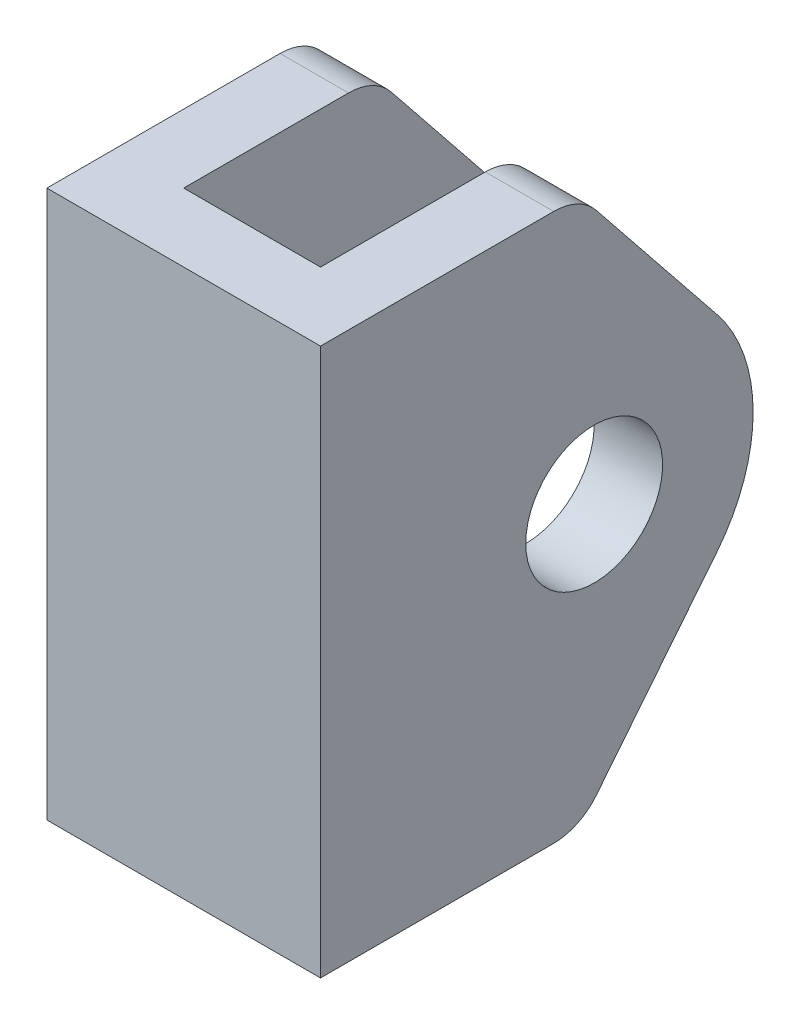
SolidWorks part; units mm, degrees
ref_plane "Front Plane" through (0, 0, 0) normal (0, 0, 1) x (1, 0, 0)
ref_plane "Top Plane" through (0, 0, 0) normal (0, 1, 0) x (1, 0, 0)
ref_plane "Right Plane" through (0, 0, 0) normal (1, 0, 0) x (0, 0, -1)
sketch "Sketch1" plane through (0, 0, 0) normal (0, 1, 0) x (1, 0, 0)
  line L0 (-21.4705, -2.672) -> (-8.7705, -2.672)
  line L1 (-8.7705, -2.672) -> (-8.7705, 19.553)
  line L2 (-8.7705, 19.553) -> (-11.9455, 19.553)
  line L3 (-11.9455, 19.553) -> (-11.9455, 0.503)
  line L4 (-11.9455, 0.503) -> (-18.2955, 0.503)
  line L5 (-18.2955, 0.503) -> (-18.2955, 19.553)
  line L6 (-18.2955, 19.553) -> (-21.4705, 19.553)
  line L7 (-21.4705, 19.553) -> (-21.4705, -2.672)
  dimension "D1" = 3.175
  dimension "D2" = 6.35
  dimension "D3" = 19.05
  dimension "D4" = 3.175
extrude "Boss-Extrude1" add sketch "Sketch1" along normal blind 12.7 and the other way blind 12.7 contours L7 L0 L1 L2 L3 L4 L5 L6
sketch "Sketch3" plane through (-21.4705, 0, 0) normal (-1, 0, 0) x (0, 0, 1)
  line L1 (-10.028, -12.7) -> (-10.028, 0)
  line L2 (-19.553, -12.7) -> (2.672, -12.7) construction
  line L3 (-10.028, 0) -> (-10.028, 12.7)
  line L4 (-19.553, 12.7) -> (2.672, 12.7) construction
  line L6 (-19.553, -12.7) -> (-19.553, 12.7) construction
  circle A0 centre (-10.028, 0) radius 3.175
  dimension "D2" = 6.35
  dimension "D1" = 3.175
extrude "Cut-Extrude1" cut sketch "Sketch3" against normal through all contours L3 A0 L1 | L1 A0 L3 region at (-21.4705, 0, -11.3755) region at (-21.4705, 0, -8.6805)
sketch "Sketch5" plane through (-8.7705, 0, 0) normal (1, 0, 0) x (0, 0, -1)
  line L0 (-2.672, 12.7) -> (19.553, 12.7) construction
  line L1 (-2.672, 12.7) -> (9.3695, 12.7)
  line L2 (9.3695, 12.7) -> (19.553, 0)
  line L3 (19.553, 0) -> (9.3695, -12.7)
  line L5 (9.3695, -12.7) -> (-2.672, -12.7)
  line L6 (-2.672, -12.7) -> (-2.672, 12.7)
  line L7 (19.553, -12.7) -> (19.553, 12.7) construction
  line L8 (9.3695, 12.7) -> (19.0139, 19.0425)
  line L9 (19.0139, 19.0425) -> (26.1277, -0.4938)
  line L10 (26.1277, -0.4938) -> (24.4219, -16.6099)
  line L11 (24.4219, -16.6099) -> (9.7872, -17.8219)
  line L12 (9.7872, -17.8219) -> (9.3695, -12.7)
  line M8 (19.553, -12.7) -> (19.553, 12.7)
  line M9 (19.553, 12.7) -> (-2.672, 12.7)
  line M11 (-2.672, -12.7) -> (19.553, -12.7)
extrude "Cut-Extrude3" cut sketch "Sketch5" against normal blind 17.78 contours L2 M9 M8 | L3 M8 M11 region at (-8.7705, 8.4667, -16.1585) region at (-8.7705, -8.4667, -16.1585)
fillet "Fillet1" radius 7.62 2 edges at (-19.883, 0, -19.553) (-10.358, 0, -19.553)
fillet "Fillet2" radius 2.54 4 edges at (-19.883, -12.7, -9.3695) (-10.358, -12.7, -9.3695) (-10.358, 12.7, -9.3695) (-19.883, 12.7, -9.3695)
sketch "Sketch6" plane through (0, 0, 2.672) normal (0, 0, 1) x (1, 0, 0)
  line L0 (-8.7705, -12.7) -> (-21.4705, 12.7) construction
  circle A0 centre (-15.1205, 0) radius 3.175
  dimension "D1" = 6.35
